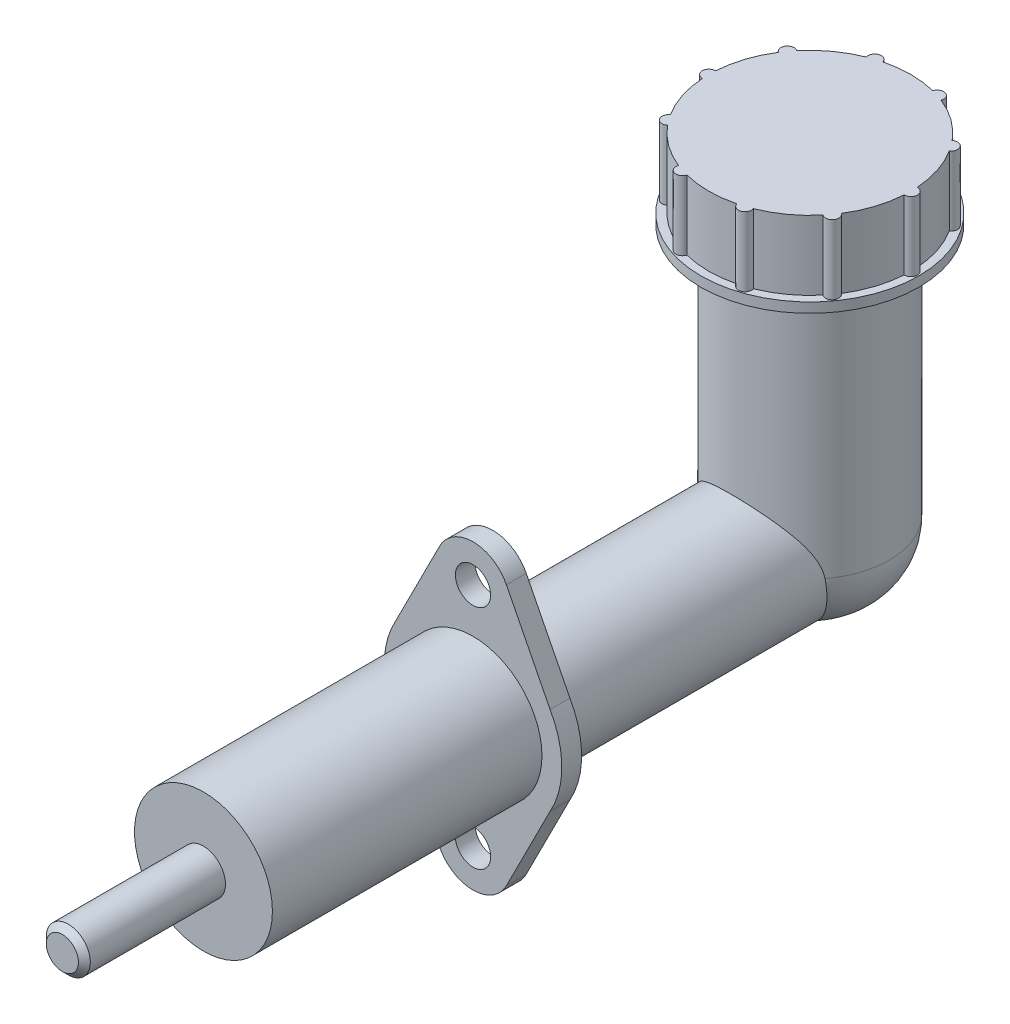
SolidWorks part; units mm, degrees
note: '?' marks a value the reader was unsure of.
ref_plane "Front Plane" through (0, 0, 0) normal (0, 0, 1) x (1, 0, 0)
ref_plane "Top Plane" through (0, 0, 0) normal (0, 1, 0) x (1, 0, 0)
ref_plane "Right Plane" through (0, 0, 0) normal (1, 0, 0) x (0, 0, -1)
sketch "Sketch1" plane through (0, 0, 0) normal (0, 0, 1) x (1, 0, 0)
  circle A0 centre (0, 0) radius 17.4
  dimension "D1" = 34.8
extrude "Boss-Extrude1" add sketch "Sketch1" along normal blind 68
ref_plane "PlaneA" through (0, 0, 0) normal (0, 0, -1) x (-1, 0, 0)
sketch "Sketch2"
  line L0 (19.4456, 11.1189) -> (8.4306, 32.8694)
  line L2 (-8.4306, 32.8694) -> (-19.4456, 11.1189)
  line L3 (-8.4306, 1032.8694) -> (-8.4306, 32.8694) construction
  line L4 (8.4306, 1032.8694) -> (8.4306, 32.8694) construction
  line L5 (-19.4456, -11.1189) -> (-8.4306, -32.8694)
  line L7 (8.4306, -32.8694) -> (19.4456, -11.1189)
  line L8 (8.4306, -32.8694) -> (8.4306, -49967.1306) construction
  line L9 (-8.4306, -32.8694) -> (-8.4306, -49967.1306) construction
  line L10 (0, 50000) -> (0, -50000) construction
  circle A0 centre (0, 28.6) radius 4.45
  circle A1 centre (0, -28.6) radius 4.45
  arc A2 (8.4306, 32.8694) -> (-8.4306, 32.8694) centre (0, 28.6) ccw
  arc A3 (-8.4306, -32.8694) -> (8.4306, -32.8694) centre (0, -28.6) ccw
  arc A4 (-19.4456, 11.1189) -> (-19.4456, -11.1189) centre (0, 0) ccw
  circle A6 centre (0, 0) radius 22.4
  arc A7 (19.4456, -11.1189) -> (19.4456, 11.1189) centre (0, 0) ccw
  point P8 (9.45, 28.6)
  point P14 (9.45, -28.6)
  dimension "D3" = 8.9
  dimension "D1" = 28.6
  dimension "D2" = 57.2
  dimension "D4" = 0
other "AlignGroup1" parameters "D3"=6.0725, "D4"=7.0403, "D9"=8.9, "D10"=9.45, "D11"=22.4, "D7"=9.45, "D1"=26.0556, "D2"=57.9624, "D8"=33.9334, "D5"=0, "D12"=8.4306, "D13"=19.4456, "D6"=5
other "AlignGroup2"
extrude "Boss-Extrude3" add sketch "Sketch2" along normal blind 5 separate body
ref_plane "Planefront" through (0, 0, 68) normal (0, 0, 1) x (1, 0, 0)
ref_plane "Plane4" through (0, 0, -5) normal (0, 0, -1) x (-1, 0, 0)
sketch "Sketch4" plane through (0, 0, -5) normal (0, 0, -1) x (-1, 0, 0)
  circle A0 centre (0, 0) radius 16
  dimension "D1" = 32
extrude "Boss-Extrude4" add sketch "Sketch4" along normal blind 84.62
ref_axis "Axis1" through (0, 0, -117.1221) along (0, 0, 1)?
ref_plane "Plane6" through (0, 0, 0) normal (0, 1, 0) x (1, 0, 0)
sketch "Sketch5" plane through (0, 0, 0) normal (0, 1, 0) x (1, 0, 0)
  line L0 (0, 89.62) -> (0, 5) construction
  circle A0 centre (0, 84.9754) radius 20
  dimension "D1" = 40
extrude "Boss-Extrude5" add sketch "Sketch5" along normal mid plane 32
ref_plane "Plane8" through (0, 16, 0) normal (0, 1, 0) x (1, 0, 0)
sketch "Sketch7" plane through (0, 16, 0) normal (0, 1, 0) x (1, 0, 0)
  circle A0 centre (0, 84.9754) radius 20
  dimension "D1" = 40
extrude "Boss-Extrude6" add sketch "Sketch7" along normal blind 48.9
ref_plane "Plane9" through (0, 64.9, 0) normal (0, 1, 0) x (1, 0, 0)
sketch "Sketch8" plane through (0, 64.9, 0) normal (0, 1, 0) x (1, 0, 0)
  circle A0 centre (0, 84.9754) radius 27.5
  dimension "D1" = 55
extrude "Boss-Extrude7" add sketch "Sketch8" along normal blind 2.5
ref_plane "Plane10" through (0, 67.4, 0) normal (0, 1, 0) x (1, 0, 0)
sketch "Sketch10" plane through (0, 67.4, 0) normal (0, 1, 0) x (1, 0, 0)
  arc A0 (-25.4466, 83.3262) -> (-21.5561, 71.3524) centre (0, 84.9754) ccw
  circle A1 centre (0, 84.9754) radius 27.2 construction
  arc A2 (-25.4466, 86.6245) -> (-25.4466, 83.3262) centre (-25.5, 84.9754) ccw
  arc A3 (-19.6174, 101.2667) -> (-21.5561, 98.5983) centre (-20.6299, 99.9639) ccw
  arc A4 (-6.295, 109.6861) -> (-9.4319, 108.6669) centre (-7.8799, 109.2273) ccw
  arc A5 (9.4319, 108.6669) -> (6.295, 109.6861) centre (7.8799, 109.2273) ccw
  arc A6 (21.5561, 98.5983) -> (19.6174, 101.2667) centre (20.6299, 99.9639) ccw
  arc A7 (25.4466, 83.3262) -> (25.4466, 86.6245) centre (25.5, 84.9754) ccw
  arc A8 (19.6174, 68.684) -> (21.5561, 71.3524) centre (20.6299, 69.9868) ccw
  arc A9 (6.295, 60.2646) -> (9.4319, 61.2838) centre (7.8799, 60.7234) ccw
  arc A10 (-9.4319, 61.2838) -> (-6.295, 60.2646) centre (-7.8799, 60.7234) ccw
  arc A11 (-21.5561, 71.3524) -> (-19.6174, 68.684) centre (-20.6299, 69.9868) ccw
  arc A12 (-6.295, 60.2646) -> (6.295, 60.2646) centre (0, 84.9754) ccw
  arc A13 (-19.6174, 68.684) -> (-9.4319, 61.2838) centre (0, 84.9754) ccw
  arc A14 (9.4319, 61.2838) -> (19.6174, 68.684) centre (0, 84.9754) ccw
  arc A15 (21.5561, 71.3524) -> (25.4466, 83.3262) centre (0, 84.9754) ccw
  arc A16 (19.6174, 101.2667) -> (9.4319, 108.6669) centre (0, 84.9754) ccw
  arc A17 (6.295, 109.6861) -> (-6.295, 109.6861) centre (0, 84.9754) ccw
  arc A18 (-9.4319, 108.6669) -> (-19.6174, 101.2667) centre (0, 84.9754) ccw
  arc A19 (-21.5561, 98.5983) -> (-25.4466, 86.6245) centre (0, 84.9754) ccw
  arc A20 (25.4466, 86.6245) -> (21.5561, 98.5983) centre (0, 84.9754) ccw
  point P35 (0, 84.9754)
  dimension "D1" = 51
  dimension "D2" = 54.4
  dimension "D3" = 3.3
  dimension "D4" = 10
extrude "Boss-Extrude9" add sketch "Sketch10" along normal blind 17.5
fillet "Fillet11" radius 17.5 2 edges at (2.7057, 15.7696, -65.1592) (-20, -16, -84.9754)
sketch "Sketch11" plane through (0, 0, 68) normal (0, 0, 1) x (1, 0, 0)
  circle A0 centre (0, 0) radius 5.5532
  dimension "D1" = 11.1064
extrude "Boss-Extrude10" add sketch "Sketch11" along normal blind 35.6
cosmetic thread "Cosmetic Thread8" parameters "D1"=35.6, "D2"=6.6777
chamfer "Chamfer1" distance 1.5 angle 45 1 edges at (5.5532, 0, 103.6)
sketch "Sketch23" plane through (0, 0, 103.6) normal (0, 0, 1) x (1, 0, 0)
  circle A1 centre (0, 0) radius 4.0532
  circle A2 centre (0, 0) radius 4.0532
  dimension "D1" = 0
ref_axis "Axis2" through (0, 64.9, -84.9754) along (0, -1, 0)?
ref_point "Point1"
ref_point "Point2"
ref_point "Point3"
ref_axis "Axis3" through (0, 0, -5) along (0, 0.7279, -0.6857)?
sketch "Sketch24" plane through (0, 64.9, 0) normal (0, 1, 0) x (1, 0, 0)
  line L0 (-148.9804, 120.9767) -> (148.9804, 120.9767)
  point P3 (0, 120.9767)
  point P6 (5.3531, -60.0697)
ref_point "Point4"
ref_point "Point5"
